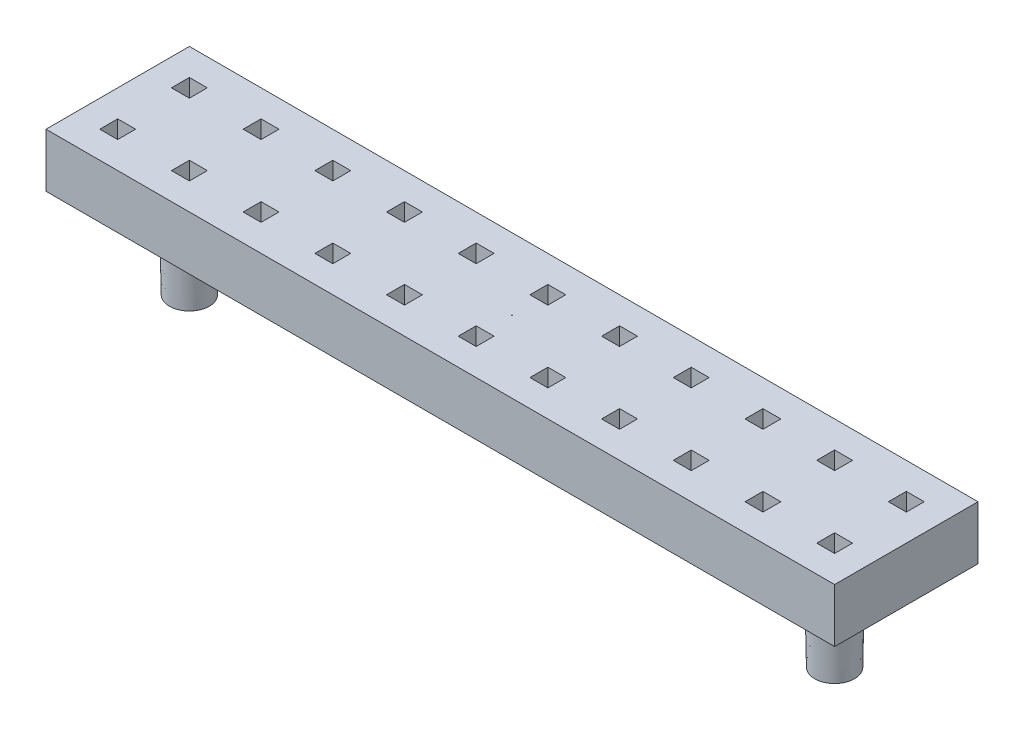
SolidWorks part; units mm, degrees
ref_plane "Front Plane" through (0, 0, 0) normal (0, 0, 1) x (1, 0, 0)
ref_plane "Top Plane" through (0, 0, 0) normal (0, 1, 0) x (1, 0, 0)
ref_plane "Right Plane" through (0, 0, 0) normal (1, 0, 0) x (0, 0, -1)
sketch "Sketch1" plane through (0, 0, 0) normal (0, 1, 0) x (1, 0, 0)
  line L1 (0, 0) -> (22, 0)
  line L2 (0, 0) -> (0, 4)
  line L3 (0, 4) -> (22, 4)
  line L4 (22, 0) -> (22, 4)
extrude "Boss-Extrude1" add sketch "Sketch1" along normal blind 1.5
sketch "Sketch2" plane through (0, 1.5, 0) normal (0, 1, 0) x (1, 0, 0)
  line L0 (2.75, 3.25) -> (2.75, 2.75)
  line L1 (0.75, 3.25) -> (1.25, 3.25)
  line L2 (0.75, 3.25) -> (0.75, 2.75)
  line L3 (0.75, 2.75) -> (1.25, 2.75)
  line L4 (1.25, 3.25) -> (1.25, 2.75)
  line L5 (2.75, 3.25) -> (3.25, 3.25)
  line L6 (3.25, 3.25) -> (3.25, 2.75)
  line L7 (2.75, 2.75) -> (3.25, 2.75)
  line L8 (4.75, 3.25) -> (4.75, 2.75)
  line L9 (4.75, 3.25) -> (5.25, 3.25)
  line L10 (5.25, 3.25) -> (5.25, 2.75)
  line L11 (4.75, 2.75) -> (5.25, 2.75)
  line L12 (6.75, 3.25) -> (6.75, 2.75)
  line L13 (6.75, 3.25) -> (7.25, 3.25)
  line L14 (7.25, 3.25) -> (7.25, 2.75)
  line L15 (6.75, 2.75) -> (7.25, 2.75)
  line L16 (8.75, 3.25) -> (8.75, 2.75)
  line L17 (8.75, 3.25) -> (9.25, 3.25)
  line L18 (9.25, 3.25) -> (9.25, 2.75)
  line L19 (8.75, 2.75) -> (9.25, 2.75)
  line L20 (10.75, 3.25) -> (10.75, 2.75)
  line L21 (10.75, 3.25) -> (11.25, 3.25)
  line L22 (11.25, 3.25) -> (11.25, 2.75)
  line L23 (10.75, 2.75) -> (11.25, 2.75)
  line L24 (12.75, 3.25) -> (12.75, 2.75)
  line L25 (12.75, 3.25) -> (13.25, 3.25)
  line L26 (13.25, 3.25) -> (13.25, 2.75)
  line L27 (12.75, 2.75) -> (13.25, 2.75)
  line L28 (14.75, 3.25) -> (14.75, 2.75)
  line L29 (14.75, 3.25) -> (15.25, 3.25)
  line L30 (15.25, 3.25) -> (15.25, 2.75)
  line L31 (14.75, 2.75) -> (15.25, 2.75)
  line L32 (16.75, 3.25) -> (16.75, 2.75)
  line L33 (16.75, 3.25) -> (17.25, 3.25)
  line L34 (17.25, 3.25) -> (17.25, 2.75)
  line L35 (16.75, 2.75) -> (17.25, 2.75)
  line L36 (18.75, 3.25) -> (18.75, 2.75)
  line L37 (18.75, 3.25) -> (19.25, 3.25)
  line L38 (19.25, 3.25) -> (19.25, 2.75)
  line L39 (18.75, 2.75) -> (19.25, 2.75)
  line L40 (20.75, 3.25) -> (20.75, 2.75)
  line L41 (20.75, 3.25) -> (21.25, 3.25)
  line L42 (21.25, 3.25) -> (21.25, 2.75)
  line L43 (20.75, 2.75) -> (21.25, 2.75)
  line L72 (0.75, 1.25) -> (0.75, 0.75)
  line L73 (0.75, 1.25) -> (1.25, 1.25)
  line L74 (1.25, 1.25) -> (1.25, 0.75)
  line L75 (0.75, 0.75) -> (1.25, 0.75)
  line L76 (2.75, 1.25) -> (2.75, 0.75)
  line L77 (2.75, 1.25) -> (3.25, 1.25)
  line L78 (3.25, 1.25) -> (3.25, 0.75)
  line L79 (2.75, 0.75) -> (3.25, 0.75)
  line L80 (4.75, 1.25) -> (4.75, 0.75)
  line L81 (4.75, 1.25) -> (5.25, 1.25)
  line L82 (5.25, 1.25) -> (5.25, 0.75)
  line L83 (4.75, 0.75) -> (5.25, 0.75)
  line L84 (6.75, 1.25) -> (6.75, 0.75)
  line L85 (6.75, 1.25) -> (7.25, 1.25)
  line L86 (7.25, 1.25) -> (7.25, 0.75)
  line L87 (6.75, 0.75) -> (7.25, 0.75)
  line L88 (8.75, 1.25) -> (8.75, 0.75)
  line L89 (8.75, 1.25) -> (9.25, 1.25)
  line L90 (9.25, 1.25) -> (9.25, 0.75)
  line L91 (8.75, 0.75) -> (9.25, 0.75)
  line L92 (10.75, 1.25) -> (10.75, 0.75)
  line L93 (10.75, 1.25) -> (11.25, 1.25)
  line L94 (11.25, 1.25) -> (11.25, 0.75)
  line L95 (10.75, 0.75) -> (11.25, 0.75)
  line L96 (12.75, 1.25) -> (12.75, 0.75)
  line L97 (12.75, 1.25) -> (13.25, 1.25)
  line L98 (13.25, 1.25) -> (13.25, 0.75)
  line L99 (12.75, 0.75) -> (13.25, 0.75)
  line L100 (14.75, 1.25) -> (14.75, 0.75)
  line L101 (14.75, 1.25) -> (15.25, 1.25)
  line L102 (15.25, 1.25) -> (15.25, 0.75)
  line L103 (14.75, 0.75) -> (15.25, 0.75)
  line L104 (16.75, 1.25) -> (16.75, 0.75)
  line L105 (16.75, 1.25) -> (17.25, 1.25)
  line L106 (17.25, 1.25) -> (17.25, 0.75)
  line L107 (16.75, 0.75) -> (17.25, 0.75)
  line L108 (18.75, 1.25) -> (18.75, 0.75)
  line L109 (18.75, 1.25) -> (19.25, 1.25)
  line L110 (19.25, 1.25) -> (19.25, 0.75)
  line L111 (18.75, 0.75) -> (19.25, 0.75)
  line L112 (20.75, 1.25) -> (20.75, 0.75)
  line L113 (20.75, 1.25) -> (21.25, 1.25)
  line L114 (21.25, 1.25) -> (21.25, 0.75)
  line L115 (20.75, 0.75) -> (21.25, 0.75)
  dimension "D1" = 11
  dimension "D2" = 2
extrude "Cut-Extrude1" cut sketch "Sketch2" against normal blind 2
sketch "Sketch3" plane through (0, 1.5, 0) normal (0, 1, 0) x (1, 0, 0)
  circle A0 centre (11, 2) radius 0.01
  point P0 (11, 2)
ref_axis "Axis1" [suppressed] through (11, -5.3844, -2) along (0, 1, 0)
extrude "Cut-Extrude2" cut sketch "Sketch3" against normal blind 1.5
ref_plane "Plane1" through (2.431, 0, -5.6724) normal (-0.3939, 0, 0.9191) x (0.9191, 0, 0.3939)
ref_plane "Plane2" through (0.9828, 0, 2.2931) normal (-0.3939, 0, -0.9191) x (-0.9191, 0, 0.3939)
ref_axis "Axis2" through (11, -0.075, -2) along (0, 1, 0)
sketch "Sketch4" plane through (0, 0, 0) normal (0, -1, 0) x (-1, 0, 0)
  line L0 (-19.25, 1.25) -> (-20.75, 2.75) construction
  line L1 (-20.75, 1.25) -> (-19.25, 2.75) construction
  line L3 (-19.25, 3.25) -> (-19.25, 2.75) construction
  line L4 (-1.25, 1.25) -> (-2.75, 2.75) construction
  line L6 (-2.75, 1.25) -> (-1.25, 2.75) construction
  circle A0 centre (-20, 2) radius 0.6
  circle A1 centre (-2, 2) radius 0.6
extrude "Boss-Extrude2" add sketch "Sketch4" along normal blind 2.5 draft 1
ref_axis "Axis3" through (20, 0, -2) along (0, -1, 0)
ref_axis "Axis4" through (2, 0, -2) along (0, -1, 0)
